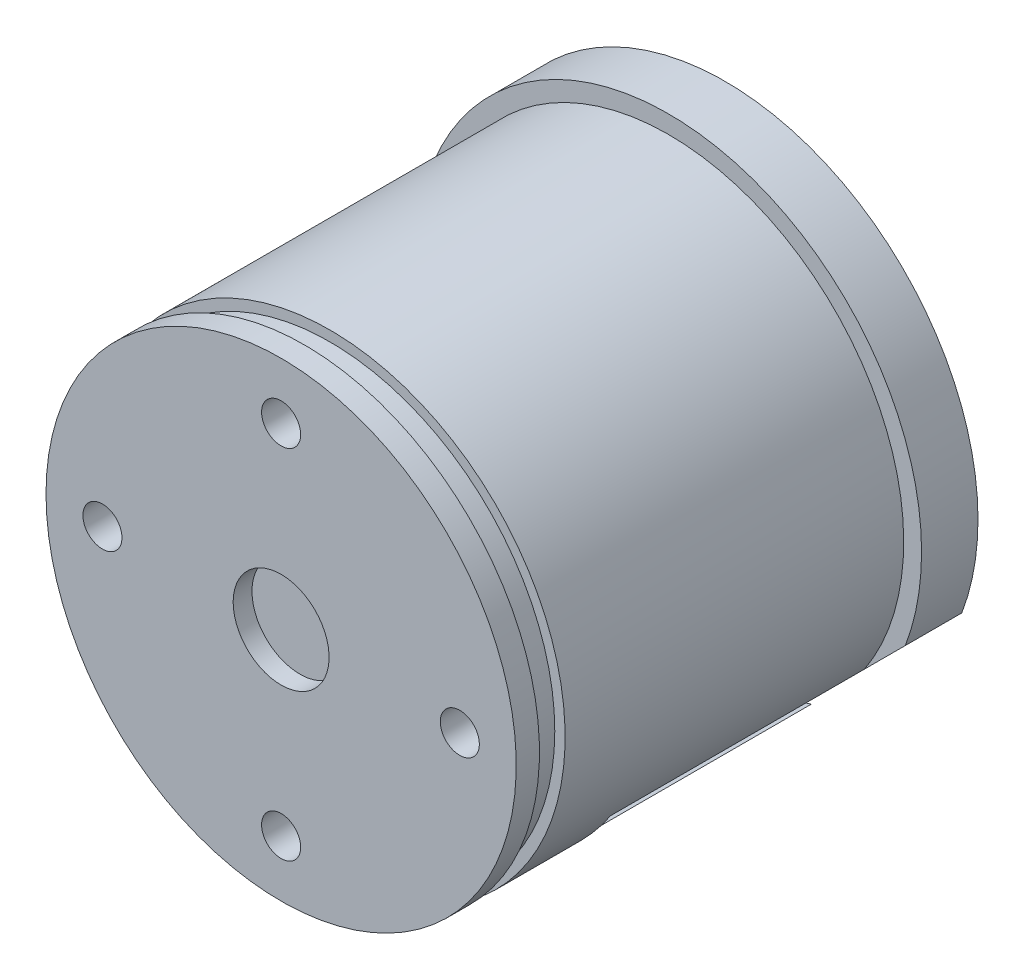
SolidWorks part; units mm, degrees
ref_plane "Front Plane" through (0, 0, 0) normal (0, 0, 1) x (1, 0, 0)
ref_plane "Top Plane" through (0, 0, 0) normal (0, 1, 0) x (1, 0, 0)
ref_plane "Right Plane" through (0, 0, 0) normal (1, 0, 0) x (0, 0, -1)
ref_axis "Z" through (0, 0, 21.78) along (0, 0, -1)
ref_plane "Plane1" through (0, 0, 0) normal (0.7071, 0.7071, 0) x (0, 0, -1)
sketch "Sketch10" plane through (0, 0, 0) normal (0, 1, 0) x (1, 0, 0)
  line L0 (-13.45, 3) -> (0, 3)
  line L1 (0, 38.469) -> (0, 33.6342) construction
  line L2 (0, -21.78) -> (0, 4.18) construction
  line L3 (-13.45, 3) -> (-13.45, 0)
  line L4 (-13.45, 0) -> (-12.5, 0)
  line L5 (-12.5, 0) -> (-12.5, -18)
  line L6 (-12.5, -18) -> (-11.95, -18)
  line L7 (-11.95, -18) -> (-11.95, -19.365)
  line L8 (-11.95, -19.365) -> (-12.5, -19.365)
  line L9 (-12.5, -19.365) -> (-12.5, -20.6)
  line L10 (-12.5, -20.6) -> (-2.55, -20.6)
  line L11 (-2.55, -20.6) -> (-2.55, -19.6)
  line L12 (-2.55, -19.6) -> (0, -19.6)
  line L13 (0, -19.6) -> (0, 3)
  dimension "D1" = 25
  dimension "D2" = 26.9
  dimension "D4" = 3
  dimension "D3" = 20.6
  dimension "D5" = 18
  dimension "D6" = 1.365
  dimension "D7" = 23.9
  dimension "D8" = 1
  dimension "D9" = 5.1
revolve "Revolve1" add sketch "Sketch10" angle 360 about L1
sketch "Sketch11" plane through (0, 0, 0) normal (0, 0, 1) x (1, 0, 0)
  line L0 (9.5, 0) -> (0, 0) construction
  circle A0 centre (9.5, 0) radius 1.0386
  dimension "D1" = 9.5
extrude "Cut-Extrude1" cut sketch "Sketch11" against normal through all both and the other way through all
pattern_circular "CirPattern1" count 4 over 360 about axis through (0, 0, 21.78) along (0, 0, -1) of "Cut-Extrude1"
sketch "Sketch14" plane through (0, 0, 0) normal (0, 0, 1) x (1, 0, 0)
  line L0 (0, 0) -> (8.8388, -8.8388) construction
  line L1 (0.9621, -3.3744) -> (-1.432, 3.2034) construction
  line L2 (8.8388, -8.8388) -> (17.6777, 0) construction
  line L3 (2.7236, -7.4831) -> (0, 0) construction
  line L4 (0, 0) -> (-4.6648, 0) construction
  line L5 (2.4887, -7.5686) -> (-0.2349, -0.0855)
  line L6 (9.0156, -9.0156) -> (17.8544, -0.1768)
  line L7 (8.6621, -8.6621) -> (17.5009, 0.1768)
  line L8 (2.9586, -7.3976) -> (0.2349, 0.0855)
  line L9 (17.8544, -0.1768) -> (17.5009, 0.1768)
  line L13 (-0.2349, -0.0855) -> (0.2349, 0.0855) construction
  line L14 (-0.2349, -0.0855) -> (-1.432, 3.2034)
  line L15 (-1.432, 3.2034) -> (-0.9621, 3.3744)
  line L16 (-0.9621, 3.3744) -> (0.2349, 0.0855)
  arc A1 (8.8388, -8.8388) -> (2.7236, -7.4831) centre (6.2131, -6.2131) cw construction
  arc A2 (9.0156, -9.0156) -> (2.4887, -7.5686) centre (6.2131, -6.2131) cw
  arc A3 (8.6621, -8.6621) -> (2.9586, -7.3976) centre (6.2131, -6.2131) cw
  spline S0 degree 4 poles (-1.2346, 0.1956) (-1.1594, 0.1712) (-1.0456, 0.1376) (-0.8922, 0.0988) (-0.699, 0.0605) (-0.5436, 0.036) (-0.3885, 0.0177) (-0.2392, 0.0056) (-0.0583, -0.0003) (0.0419, -0.0006) (0.2016, 0.0042) (0.3388, 0.0133) (0.4703, 0.027) (0.604, 0.0451) (0.7704, 0.0735) (0.9678, 0.1164) (1.1954, 0.1792) (1.45, 0.268) (1.6984, 0.3733) (1.9393, 0.4945) (2.2303, 0.6648) (2.5062, 0.859) (2.869, 1.1613) (3.2868, 1.603) (3.6431, 2.0971) (3.957, 2.6954) (4.1746, 3.2624) (4.3191, 3.7825) (4.4324, 4.4059) (4.4884, 5.173) (4.4459, 5.942) (4.3132, 6.6995) (4.1345, 7.3498) (3.9563, 7.859) (3.6924, 8.4793) (3.313, 9.195) (2.8641, 9.8691) (2.3956, 10.4455) (2.0309, 10.8412) (1.7446, 11.1295) (1.4543, 11.4041) (1.1404, 11.6736) (0.8355, 11.9175) (0.5472, 12.1296) (0.3617, 12.2629) (0.0858, 12.4456) (-0.0439, 12.5287) (-0.2722, 12.6693) (-0.4394, 12.767) (-0.6227, 12.8706) (-0.8036, 12.9685) (-0.9875, 13.064) (-1.1725, 13.1561) (-1.3126, 13.2229) (-1.4064, 13.2663) (-1.4535, 13.2878) knots 0 0 0 0 0 0.016254 0.024381 0.032508 0.04051 0.048511 0.056512 0.064513 0.071439 0.078366 0.085293 0.092219 0.099146 0.106072 0.119925 0.133778 0.147631 0.161484 0.175337 0.18919 0.216896 0.23075 0.272309 0.313868 0.341574 0.36928 0.396986 0.424692 0.471658 0.52707 0.554776 0.582483 0.610189 0.637895 0.693307 0.748719 0.776425 0.790278 0.804131 0.831837 0.859543 0.873397 0.88725 0.901103 0.914956 0.925586 0.936217 0.946847 0.957478 0.968108 0.978739 0.989369 1 1 1 1 1 construction
  spline S1 degree 4 poles (0, 0) (0.0287, 0) (0.0863, 0.0008) (0.2016, 0.0042) (0.3388, 0.0133) (0.4703, 0.027) (0.604, 0.0451) (0.7704, 0.0735) (0.9678, 0.1164) (1.1954, 0.1792) (1.45, 0.268) (1.6984, 0.3733) (1.9393, 0.4945) (2.2303, 0.6648) (2.5062, 0.859) (2.869, 1.1613) (3.2868, 1.603) (3.6431, 2.0971) (3.957, 2.6954) (4.1746, 3.2624) (4.3191, 3.7825) (4.4324, 4.4059) (4.4884, 5.173) (4.4459, 5.942) (4.3132, 6.6995) (4.1345, 7.3498) (3.9563, 7.859) (3.6924, 8.4793) (3.313, 9.195) (2.8641, 9.8691) (2.3956, 10.4455) (2.0309, 10.8412) (1.7446, 11.1295) (1.4543, 11.4041) (1.1404, 11.6736) (0.8355, 11.9175) (0.5472, 12.1296) (0.3617, 12.2629) (0.142, 12.4084) (0.0483, 12.4692) (0, 12.5) knots 0.064513 0.064513 0.064513 0.064513 0.064513 0.071439 0.078366 0.085293 0.092219 0.099146 0.106072 0.119925 0.133778 0.147631 0.161484 0.175337 0.18919 0.216896 0.23075 0.272309 0.313868 0.341574 0.36928 0.396986 0.424692 0.471658 0.52707 0.554776 0.582483 0.610189 0.637895 0.693307 0.748719 0.776425 0.790278 0.804131 0.831837 0.859543 0.873397 0.88725 0.901103 0.914956 0.914956 0.914956 0.914956 0.914956 construction
  dimension "D1" = 12.5
  dimension "D3" = 45
  dimension "D2" = 70
  dimension "D6" = 7
  dimension "D4" = 0.25
  dimension "D5" = 0.25
extrude "Cut-Extrude2" cut sketch "Sketch14" against normal through all and the other way blind 13.5
sketch "Sketch15" plane through (0, 0, 0) normal (0, 0, 1) x (1, 0, 0)
  line L0 (13.8414, -3.4827) -> (4.053, -13.2711)
  line L1 (4.053, -13.2711) -> (6.247, -15.4651)
  line L2 (6.247, -15.4651) -> (16.0354, -5.6767)
  line L3 (16.0354, -5.6767) -> (13.8414, -3.4827)
  line L4 (10.421, -6.9032) -> (12.5889, -4.7352) construction
extrude "Cut-Extrude3" cut sketch "Sketch15" against normal through all
sketch "Sketch17" plane through (0, 0, -3) normal (0, 0, -1) x (-1, 0, 0)
  line L0 (1.432, 3.2034) -> (0.2349, -0.0855)
  line L1 (0.2349, -0.0855) -> (-0.9621, -3.3744)
  line L2 (0.2349, -0.0855) -> (0, 0) construction
  line L4 (1.432, 3.2034) -> (-2.4887, -7.5686) construction
  line L5 (1.432, 3.2034) -> (-3.2665, 4.9135)
  line L6 (-4.5482, 4.3158) -> (-6.2583, -0.3826)
  line L7 (-5.6606, -1.6643) -> (-0.9621, -3.3744)
  arc A0 (-5.6606, -1.6643) -> (-6.2583, -0.3826) centre (-5.3186, -0.7246) cw
  arc A1 (-3.2665, 4.9135) -> (-4.5482, 4.3158) centre (-3.6085, 3.9738) ccw
  point P2 (-3.5323, 5.0103)
  point P15 (-4.2062, 5.2555)
  dimension "D2" = 1
  dimension "D1" = 6
extrude "Cut-Extrude5" cut sketch "Sketch17" against normal blind 1
equation "\"BearingBaseDistance\"= 10"
equation "\"BearingOD\"= 32"
equation "\"BearingHeight\"= 4"
equation "\"SeatsOD\"= \"BearingOD\" + 10"
equation "\"WireHarnessHeight\"= 4"
equation "\"OuterWallWidth\"= 6"
equation "\"OverallOD\" = 45"
equation "\"RetainingRingThickness\" = 1.30"
equation "\"RetaininRingGrooveDiameter\" = 23.9"
equation "\"ShaftLengthAfterFlange\" = 2*\"BearingHeight\" + \"BearingBaseDistance\" + \"RetainingRingThickness\"*2\t'give a retaining ring thickness of extra clearance"
equation "\"RetainingRingGrooveBase\" = \"ShaftLengthAfterFlange\" - \"RetainingRingThickness\"*2"
equation "\"BearingID\" = 25"
equation "\"CoverClearance\" = 1"
equation "\"CoverThickness\" = 1"
equation "\"FlangHeight\" = 3"
equation "\"OuterHousingHeight\" = \"WireHarnessHeight\" + \"BearingHeight\"*2 + \"BearingBaseDistance\""
equation "\"PCBWidth\" = 5"
equation "\"PCBHeight\" = \"OuterHousingHeight\" "
equation "\"PCBThickness\" = 1"
equation "\"NormalDistSidewallPCBToZ\" = (\"OverallOD\"/2) - 1.6\t'radial distance from the z axis to pcb origin on the top/connector side"
equation "\"PCBSidewallCutoutClearance\" = 0.1"
equation "\"OutputHubBoltCircleRadius\" = 8"
equation "\"OutputHubOD\" = 27"
equation "\"StatorWireRadius\" = \"NormalDistSidewallPCBToZ\" - 5.7"
equation "\"MountingHoleRadius\" = (\"OverallOD\"+\"BearingOD\")/4"
equation "\"D1@Sketch10\"=\"BearingID\""
equation "\"BearingInnerRaceOD\" = 26.9"
equation "\"D2@Sketch10\"=\"BearingInnerRaceOD\""
equation "\"D4@Sketch10\"=\"FlangHeight\""
equation "\"D3@Sketch10\"=\"ShaftLengthAfterFlange\""
equation "\"D5@Sketch10\"=\"RetainingRingGrooveBase\""
equation "\"D6@Sketch10\"=\"RetainingRingThickness\"*1.05"
equation "\"D7@Sketch10\"=\"RetaininRingGrooveDiameter\""
equation "\"D1@Sketch11\"=round(\"BearingID\"*0.75)/2"
equation "\"D1@Sketch14\"=\"BearingID\"/2"
